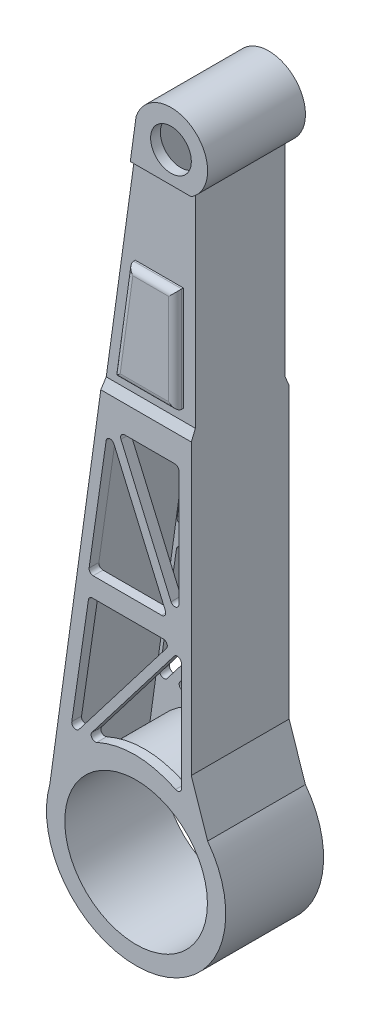
SolidWorks part; units mm, degrees
material "Beryllium"
ref_plane "Front Plane" through (0, 0, 0) normal (0, 0, 1) x (1, 0, 0)
ref_plane "Top Plane" through (0, 0, 0) normal (0, 1, 0) x (1, 0, 0)
ref_plane "Right Plane" through (0, 0, 0) normal (1, 0, 0) x (0, 0, -1)
sketch "Sketch1" plane through (0, 0, 0) normal (0, 0, 1) x (1, 0, 0)
  line L1 (-105.8406, 29.9627) -> (0, 792.4014)
  line L3 (87.7327, 66.3549) -> (67.7156, 126.0045)
  line L4 (67.7156, 126.0045) -> (67.7156, 740.9365)
  arc A0 (-105.8406, 29.9627) -> (87.7327, 66.3549) centre (0, 0) ccw
  arc A1 (67.7156, 740.9365) -> (0, 792.4014) centre (42.7609, 778.3833) ccw
  dimension "D1" = 220
  dimension "D3" = 90
extrude "Boss-Extrude1" add sketch "Sketch1" along normal blind 120
sketch "Sketch2" plane through (0, 0, 120) normal (0, 0, 1) x (1, 0, 0)
  circle A0 centre (0, 0) radius 87.5
  dimension "D1" = 175
extrude "Cut-Extrude1" cut sketch "Sketch2" against normal blind 120
sketch "Sketch3" plane through (0, 0, 120) normal (0, 0, 1) x (1, 0, 0)
  circle A0 centre (42.7609, 778.3833) radius 25
  dimension "D1" = 50
extrude "Cut-Extrude2" cut sketch "Sketch3" against normal blind 120
sketch "Sketch4" plane through (0, 0, 120) normal (0, 0, 1) x (1, 0, 0)
  line L0 (-54.201, 110.8938) -> (46.6337, 242.2671)
  line L1 (55.6001, 239.2228) -> (55.6001, 106.0656)
  line L2 (-53.5531, 253.949) -> (33.2875, 253.949)
  line L3 (37.2538, 245.9047) -> (-70.0053, 106.1614)
  line L4 (-78.9191, 109.9286) -> (-58.5005, 249.6719)
  line L5 (-52.7322, 278.0374) -> (31.3762, 278.0374)
  line L6 (35.9641, 285.0253) -> (-27.2267, 430.8679)
  line L7 (-36.764, 429.5899) -> (-57.6816, 283.7473)
  line L8 (-14.0096, 447.0874) -> (47.4631, 447.0874)
  line L9 (52.4631, 442.0874) -> (52.4631, 300.2102)
  line L10 (42.8752, 298.2224) -> (-18.5975, 440.0996)
  line L11 (67.7156, 126.0045) -> (67.7156, 740.9365) construction
  arc A0 (55.6001, 106.0656) -> (48.4562, 101.5485) centre (50.6001, 106.0656) cw
  arc A1 (-48.2034, 103.2807) -> (-54.201, 110.8938) centre (-50.2347, 107.8495) cw
  arc A2 (46.6337, 242.2671) -> (55.6001, 239.2228) centre (50.6001, 239.2228) cw
  arc A3 (-70.0053, 106.1614) -> (-78.9191, 109.9286) centre (-73.9716, 109.2057) cw
  arc A4 (33.2875, 253.949) -> (37.2538, 245.9047) centre (33.2875, 248.949) cw
  arc A5 (-53.5531, 253.949) -> (-58.5005, 249.6719) centre (-53.5531, 248.949) ccw
  arc A6 (52.4631, 442.0874) -> (47.4631, 447.0874) centre (47.4631, 442.0874) ccw
  arc A7 (52.4631, 300.2102) -> (42.8752, 298.2224) centre (47.4631, 300.2102) cw
  arc A8 (-18.5975, 440.0996) -> (-14.0096, 447.0874) centre (-14.0096, 442.0874) cw
  arc A9 (35.9641, 285.0253) -> (31.3762, 278.0374) centre (31.3762, 283.0374) cw
  arc A10 (-52.7322, 278.0374) -> (-57.6816, 283.7473) centre (-52.7322, 283.0374) cw
  arc A11 (-27.2267, 430.8679) -> (-36.764, 429.5899) centre (-31.8146, 428.88) ccw
  spline S0 degree 3 poles (-48.2034, 103.2807) (-32.2977, 110.3523) (0.4906, 117.217) (32.1407, 109.2922) (48.4562, 101.5485) knots 0.164763 0.164763 0.164763 0.164763 0.551333 0.942879 0.942879 0.942879 0.942879
  point P16 (55.6001, 253.949)
  point P41 (-34.2544, 447.0874)
  dimension "D1" = 5
  dimension "D2" = 5
shell "Shell2" thickness 12 removed face at (67.7609, 778.3833, 0)
extrude "Cut-Extrude4" cut sketch "Sketch4" against normal blind 120
sketch "Sketch6" plane through (67.7156, 0, 0) normal (1, 0, 0) x (0, 0, -1)
  line L0 (-120, 480.3553) -> (-115, 492.3949)
  line L1 (-120, 740.9365) -> (-115, 740.9365)
  line L2 (-120, 740.9365) -> (-120, 480.3553)
  line L4 (-115, 740.9365) -> (-115, 492.3949)
  line L5 (0, 740.9365) -> (-5, 740.9365)
  line L6 (0, 740.9365) -> (0, 480.3553)
  line L8 (-5, 740.9365) -> (-5, 492.3949)
  line L9 (0, 480.3553) -> (-5, 492.3949)
extrude "Cut-Extrude5" cut sketch "Sketch6" against normal blind 120
sketch "Sketch7" plane through (0, 0, 115) normal (0, 0, 1) x (1, 0, 0)
  line L0 (-5.9721, 634.1646) -> (52.957, 634.1646)
  line L1 (52.957, 634.1646) -> (52.957, 506.2348)
  line L2 (52.957, 506.2348) -> (-23.7311, 506.2348)
  line L3 (-23.7311, 506.2348) -> (-5.9721, 634.1646)
  line L4 (-41.6465, 492.3949) -> (-7.1443, 740.9365) construction
sketch "Sketch9" plane through (0, 0, 5) normal (0, 0, -1) x (-1, 0, 0)
  line L0 (-52.957, 634.1646) -> (5.9721, 634.1646)
  line L1 (5.9721, 634.1646) -> (23.7311, 506.2348)
  line L2 (23.7311, 506.2348) -> (-52.957, 506.2348)
  line L3 (-52.957, 506.2348) -> (-52.957, 634.1646)
extrude "Boss-Extrude2" add sketch "Sketch9" along normal blind 10
extrude "Boss-Extrude3" add sketch "Sketch7" along normal blind 10 contours L0 L1 L2 L3
fillet "Fillet1" radius 8 8 edges at (23.4925, 634.1646, -5) (-14.8516, 570.1997, -5) (14.613, 506.2348, -5) (52.957, 570.1997, -5) (23.4925, 634.1646, 125) (52.957, 570.1997, 125) (14.613, 506.2348, 125) (-14.8516, 570.1997, 125)
